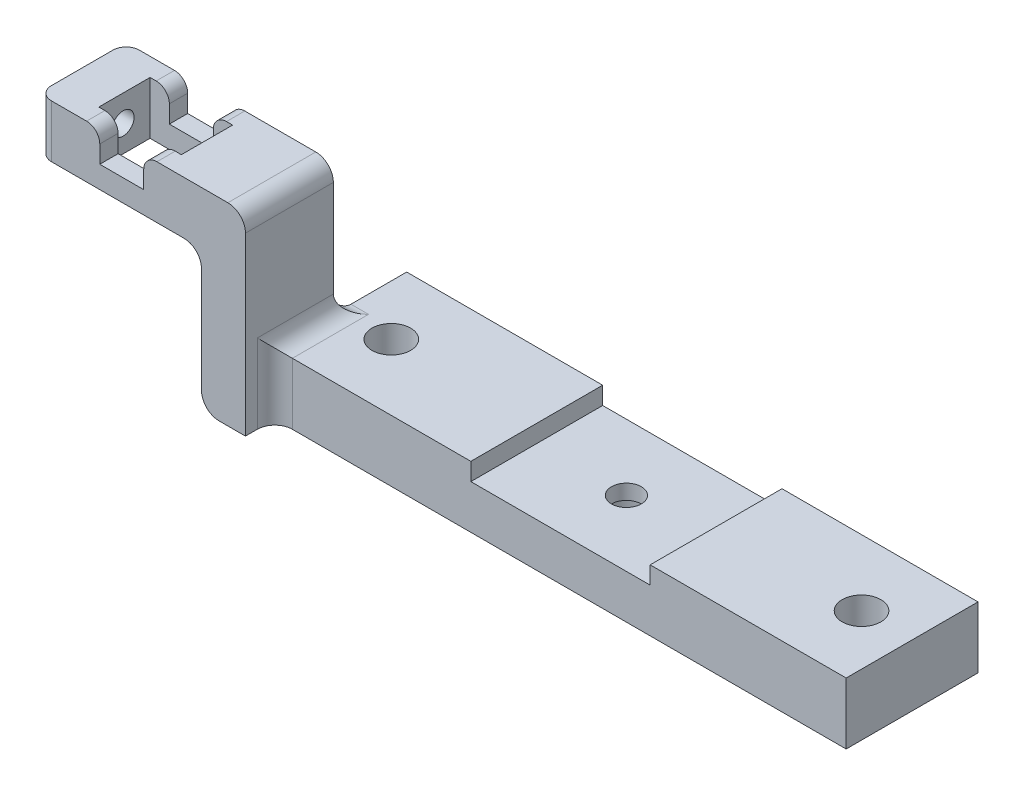
SolidWorks part; units mm, degrees
ref_plane "Front Plane" through (0, 0, 0) normal (0, 0, 1) x (1, 0, 0)
ref_plane "Top Plane" through (0, 0, 0) normal (0, 1, 0) x (1, 0, 0)
ref_plane "Right Plane" through (0, 0, 0) normal (1, 0, 0) x (0, 0, -1)
sketch "Sketch1" plane through (0, 0, 0) normal (0, 1, 0) x (1, 0, 0)
  line L1 (0, 0) -> (65, 0)
  line L2 (0, 0) -> (0, 15)
  line L3 (0, 15) -> (65, 15)
  line L4 (65, 0) -> (65, 15)
  dimension "D1" = 65
  dimension "D2" = 15
extrude "Boss-Extrude1" add sketch "Sketch1" along normal blind 7
sketch "Sketch2" plane through (0, 7, 0) normal (0, 1, 0) x (1, 0, 0)
  line L0 (65, 15) -> (0, 15) construction
  line L1 (22.3, 15) -> (42.7, 15)
  line L2 (22.3, 15) -> (22.3, 0)
  line L3 (22.3, 0) -> (42.7, 0)
  line L4 (42.7, 15) -> (42.7, 0)
  line L5 (0, 0) -> (65, 0) construction
  point P8 (32.5, 15)
  point P10 (32.5, 15)
  dimension "D1" = 20.4
extrude "Cut-Extrude1" cut sketch "Sketch2" against normal blind 2
sketch "Sketch3" plane through (0, 0, 0) normal (0, -1, 0) x (-1, 0, 0)
  line L0 (0, 15) -> (0, 0) construction
  line L1 (0, 0) -> (-65, 0) construction
  circle A0 centre (-32.5, 7.5) radius 1.7
  point P4 (0, 7.5)
  point P7 (-32.5, 0)
  dimension "D1" = 3.4
extrude "Cut-Extrude2" cut sketch "Sketch3" against normal through all
sketch "Sketch4" plane through (0, 0, 0) normal (0, -1, 0) x (-1, 0, 0)
  circle A0 centre (-32.5, 7.5) radius 3
  dimension "D1" = 6
extrude "Cut-Extrude3" cut sketch "Sketch4" against normal blind 3.3
sketch "Sketch5" plane through (0, 0, 0) normal (0, -1, 0) x (-1, 0, 0)
  line L0 (-59.25, 7.5) -> (-32.5, 7.5) construction
  line L1 (-32.5, 7.5) -> (-5.75, 7.5) construction
  circle A0 centre (-5.75, 7.5) radius 2.2
  circle A1 centre (-59.25, 7.5) radius 2.2
  dimension "D1" = 4.4
  dimension "D2" = 53.5
extrude "Cut-Extrude4" cut sketch "Sketch5" against normal through all
chamfer "Chamfer1" distance 1 angle 45 2 edges at (59.25, 0, -9.7) (5.75, 0, -9.7)
ref_plane "Plane1" through (0, 0, -7.5) normal (0, 0, -1) x (-1, 0, 0)
ref_plane "Plane2" through (0, 0, -1.658) normal (0, 0, -1) x (-1, 0, 0)
sketch "Sketch6" plane through (0, 0, -1.658) normal (0, 0, 1) x (1, 0, 0)
  line L1 (-16.575, 22) -> (-16.575, 18.5)
  line L2 (-16.575, 18.5) -> (-11.575, 18.5)
  line L3 (-11.575, 18.5) -> (-11.575, 22)
  line L4 (-11.575, 22) -> (0, 22)
  line L7 (-23.575, 16) -> (-23.575, 22)
  line L8 (-14.075, 30.6286) -> (-14.075, 5.1489) construction
  line L9 (-15.075, 53.5) -> (-15.075, 20.5) construction
  line L10 (-13.075, 20.5) -> (-13.075, 53.5) construction
  line L11 (-15.98, 19.5) -> (-12.17, 19.5) construction
  line L16 (-23.575, 16) -> (-5, 16)
  line L18 (0, 22) -> (0, 7)
  line L19 (0, 7) -> (22.3, 7) construction
  line L22 (-23.575, 22) -> (-16.575, 22)
  line L23 (0, 7) -> (0, 0) construction
  line L24 (-5, 16) -> (-5, 0)
  line L25 (-5, 0) -> (0, 0)
  line L26 (0, 7) -> (0, 0)
  dimension "D1" = 2.5
  dimension "D2" = 7
  dimension "D3" = 1
  dimension "D4" = 6
  dimension "D5" = 2.5
  dimension "D6" = 5
extrude "Boss-Extrude2" add sketch "Sketch6" along normal blind 5 and the other way blind 5
sketch "Sketch7" plane through (0, 16, 0) normal (0, -1, 0) x (1, 0, 0)
  line L0 (-14.075, 0.4889) -> (-14.075, -15.6507) construction
  line L1 (-16.575, -6.658) -> (-16.575, 3.342) construction
  line L2 (-18.52, -4.323) -> (-18.52, 1.007) construction
  line L3 (-9.63, 1.007) -> (-9.63, -4.323) construction
  line L4 (-18.52, 1.007) -> (-9.63, 1.007) construction
  line L5 (-18.52, -4.323) -> (-9.63, -4.323) construction
  line L6 (-18.77, 1.257) -> (-9.38, 1.257)
  line L7 (-9.38, 1.257) -> (-9.38, -4.573)
  line L8 (-18.77, -4.573) -> (-9.38, -4.573)
  line L9 (-18.77, -4.573) -> (-18.77, 1.257)
  line L10 (-11.575, -6.658) -> (-11.575, 3.342) construction
  line L11 (-26.757, -1.658) -> (-7.1965, -1.658) construction
  line L12 (-23.575, 3.342) -> (-5, 3.342) construction
  line L13 (-23.575, -6.658) -> (-5, -6.658) construction
  point P20 (0, 0)
  point P21 (-18.77, -9.573)
  dimension "D2" = 8.89
  dimension "D3" = 5.33
  dimension "D1" = 0.25
extrude "Cut-Extrude5" cut sketch "Sketch7" against normal through all both and the other way through all
fillet "Fillet1" radius 1.5 6 edges at (-16.575, 22, -5.6155) (-11.575, 22, -5.6155) (-11.575, 22, 2.2995) (-16.575, 22, 2.2995) (-23.575, 19, -6.658) (-23.575, 19, 3.342)
fillet "Fillet2" radius 2 2 edges at (-5, 0, -1.658) (-5, 16, -1.658)
fillet "Fillet3" radius 2 1 edges at (0, 22, -1.658)
fillet "Fillet4" radius 2 2 edges at (0, 3.5, -6.658) (0, 3.5, 0)
sketch "Sketch8" plane through (-23.575, 0, 0) normal (-1, 0, 0) x (0, 0, 1)
  line L0 (-5.158, 22) -> (1.842, 22) construction
  line L2 (-5.158, 22) -> (-5.158, 16) construction
  circle A0 centre (-1.508, 19) radius 1.25
  point P4 (0, 0)
  dimension "D1" = 2.5
  dimension "D2" = 3
  dimension "D3" = 3.65
extrude "Cut-Extrude6" cut sketch "Sketch8" against normal up to surface (4.805 mm away) up to face at (-18.77, 19, -1.658)
fillet "Fillet5" radius 2 2 edges at (-1, 7, -6.658) (0, 7, -2.329)
